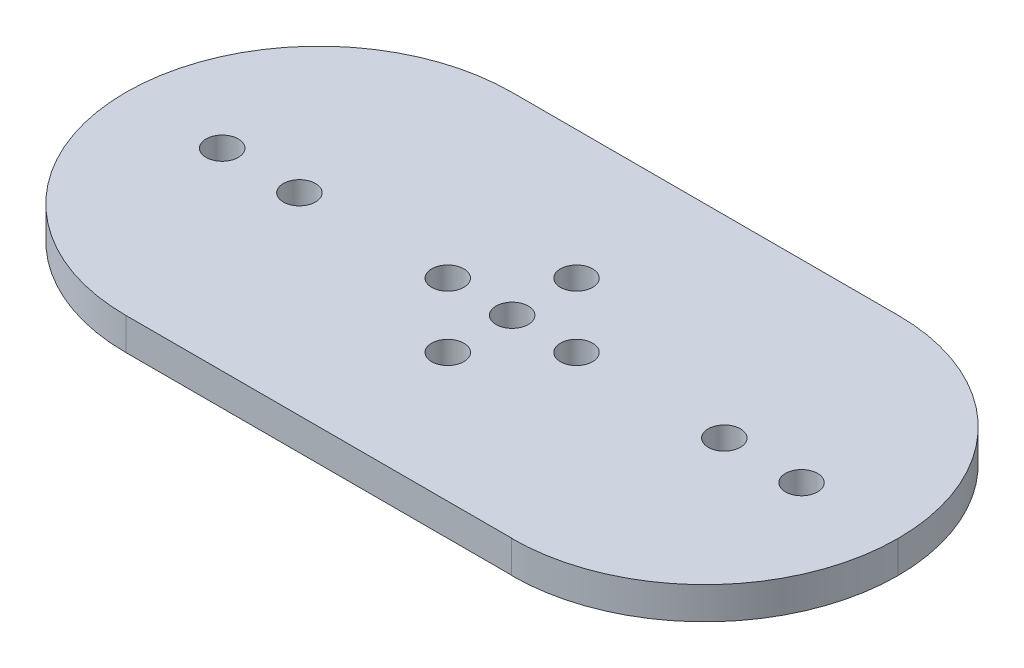
SolidWorks part; units mm, degrees
ref_plane "Front Plane" through (0, 0, 0) normal (0, 0, 1) x (1, 0, 0)
ref_plane "Top Plane" through (0, 0, 0) normal (0, 1, 0) x (1, 0, 0)
ref_plane "Right Plane" through (0, 0, 0) normal (1, 0, 0) x (0, 0, -1)
sketch "Sketch1" plane through (0, 0, 0) normal (0, 1, 0) x (1, 0, 0)
  line L0 (69.4221, 30.0207) -> (-16.2022, 30.0207) construction
  line L1 (0, 0) -> (60, 0)
  line L2 (0, 0) -> (0, 60)
  line L3 (0, 60) -> (60, 60)
  line L4 (60, 0) -> (60, 60)
  line L5 (30, 63.9004) -> (30, -4.8431) construction
  line L6 (23.4653, 40.0207) -> (37.3207, 40.0207) construction
  line L7 (20, 36.8255) -> (20, 23.5223) construction
  line L8 (23.8167, 20.0207) -> (36.7183, 20.0207) construction
  line L9 (40, 25.4802) -> (40, 39.2352) construction
  line L10 (60, 30) -> (71.5637, 30) construction
  line L11 (71.5637, 30) -> (-27.4688, 30) construction
  circle A0 centre (30, 40.0207) radius 2.5
  circle A1 centre (20, 30.0207) radius 2.5
  circle A2 centre (30, 20.0207) radius 2.5
  circle A3 centre (40, 30.0207) radius 2.5
  circle A4 centre (30, 30.0207) radius 2.5
  dimension "D3" = 5
  dimension "D4" = 5
  dimension "D5" = 5
  dimension "D6" = 5
  dimension "D11" = 5
  dimension "D1" = 60
  dimension "D2" = 60
  dimension "D7" = 10
  dimension "D8" = 10
  dimension "D9" = 10
  dimension "D10" = 10
extrude "Boss-Extrude2" add sketch "Sketch1" along normal blind 5
sketch "Sketch4" plane through (0, 0, 0) normal (0, 1, 0) x (1, 0, 0)
  line L0 (60, 29.9779) -> (-28.5402, 29.9779) construction
  line L1 (60, 60) -> (90, 60)
  line L2 (60, 60) -> (60, -0.0442)
  line L3 (60, -0.0442) -> (90, -0.0442)
  line L4 (90, 60) -> (90, -0.0442)
  line L5 (0, 60) -> (-30, 60)
  line L6 (0, 60) -> (0, 0)
  line L7 (0, 0) -> (-30, 0)
  line L8 (-30, 60) -> (-30, 0)
  line L9 (-28.5402, 29.9779) -> (117.089, 29.9779) construction
  circle A0 centre (63, 29.9779) radius 2.5
  circle A1 centre (-3, 29.9779) radius 2.5
  circle A2 centre (75, 29.9779) radius 2.5
  circle A3 centre (-15, 29.9779) radius 2.5
  dimension "D3" = 3
  dimension "D4" = 3
  dimension "D5" = 5
  dimension "D6" = 5
  dimension "D7" = 12
  dimension "D8" = 12
  dimension "D9" = 5
  dimension "D10" = 5
  dimension "D1" = 30
  dimension "D2" = 30
extrude "Boss-Extrude5" add sketch "Sketch4" along normal blind 5
fillet "Fillet1" radius 30 4 edges at (-30, 2.5, 0) (-30, 2.5, -60) (90, 2.5, 0.0442) (90, 2.5, -60)
